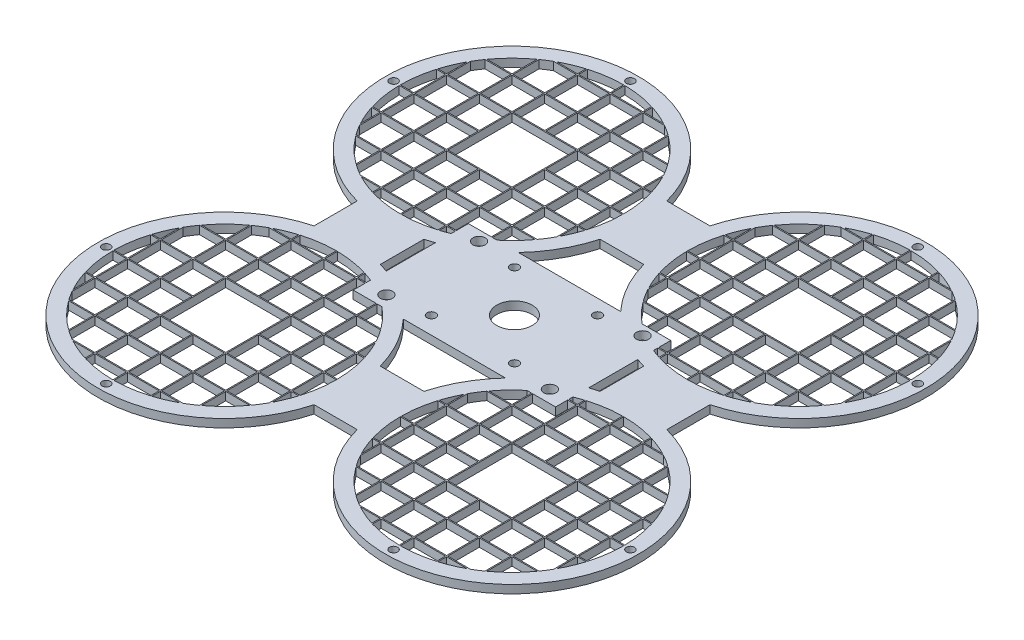
SolidWorks part; units mm, degrees
ref_plane "Front Plane" through (0, 0, 0) normal (0, 0, 1) x (1, 0, 0)
ref_plane "Top Plane" through (0, 0, 0) normal (0, 1, 0) x (1, 0, 0)
ref_plane "Right Plane" through (0, 0, 0) normal (1, 0, 0) x (0, 0, -1)
sketch "Sketch2" plane through (0, 0, 0) normal (0, 1, 0) x (1, 0, 0)
  circle A1 centre (0, 0) radius 41
  circle A2 centre (0, 0) radius 46
  point P208 (0, 0)
extrude "Boss-Extrude2" add sketch "Sketch2" along normal blind 3
sketch "Sketch4" plane through (0, 3, 0) normal (0, 1, 0) x (1, 0, 0)
  line L0 (0, 46) -> (0, 12)
  line L1 (12, 44.4072) -> (12, -44.4072)
  line L2 (24, 39.2428) -> (24, -39.2428)
  line L3 (36, 28.6356) -> (36, -28.6356)
  line L4 (-12, 44.4072) -> (-12, -44.4072)
  line L5 (-24, 39.2428) -> (-24, -32)
  line L6 (-36, 28.6356) -> (-36, -28.6356)
  line L7 (-46, 0) -> (-12, 0)
  line L8 (-44.4072, -12) -> (44.4072, -12)
  line L9 (-39.2428, -24) -> (39.2428, -24)
  line L10 (12, 0) -> (46, 0)
  line L11 (-44.4072, 12) -> (44.4072, 12)
  line L12 (-39.2428, 24) -> (39.2428, 24)
  line L13 (-28.6356, 36) -> (28.6356, 36)
  line L14 (-16, -36) -> (28.6356, -36)
  line L15 (0, -12) -> (0, -46)
  line L50 (-26.0661, -32) -> (-16, -32)
  line L52 (-26.0661, -32) -> (-26.0661, -37.902)
  line L60 (-16, -32) -> (-16, -43.1277)
  line L61 (-28.6356, -36) -> (-26.0661, -36) [skipped]
  circle A1 centre (0, 0) radius 46 construction
  circle A2 centre (0, 0) radius 46
  dimension "D1" = 4
  dimension "D2" = 4
extrude "Extrude-Thin5" add sketch "Sketch4" against normal blind 3 thin thin type one direction wall 0.4
sketch "Sketch5" plane through (0, 0, 0) normal (0, -1, 0) x (1, 0, 0)
  circle A0 centre (0, -43.4524) radius 1.5
  circle A3 centre (43.4524, 0) radius 1.5
  circle A4 centre (0, 43.4524) radius 1.5 [skipped]
  circle A5 centre (-43.4524, 0) radius 1.5 [skipped]
  point P11 (0, 0)
  dimension "D1" = 4
extrude "Cut-Extrude1" cut sketch "Sketch5" against normal blind 3
sketch "Sketch8" plane through (0, 3, 0) normal (0, 1, 0) x (1, 0, 0)
  line L1 (-16, -32) -> (-25.632, -32)
  line L2 (-16, -32) -> (-16, -37.7492)
  line L3 (-16, -37.7492) -> (-25.632, -37.7492)
  line L4 (-25.632, -32) -> (-25.632, -37.7492)
extrude "Boss-Extrude4" add sketch "Sketch8" against normal through all
sketch "Sketch9" plane through (0, 3, 0) normal (0, 1, 0) x (1, 0, 0)
  circle A3 centre (-22.2697, -36.1812) radius 2.25
extrude "Cut-Extrude3" cut sketch "Sketch9" against normal through all
ref_plane "Plane1" through (-52.73, 0, 0) normal (1, 0, 0) x (0, 0, -1)
mirror "Mirror1" about plane through (-52.73, 0, 0) normal (1, 0, 0) of bodies 159
sketch "Sketch10" plane through (0, 3, 0) normal (0, 1, 0) x (1, 0, 0)
  line L0 (-66.2554, 12) -> (-69.06, 12) construction
  line L1 (-63.5152, 12) -> (-41.7915, 12)
  line L2 (-63.5152, 12) -> (-63.5152, -12.4)
  line L3 (-63.5152, -12.4) -> (-41.7915, -12.4)
  line L4 (-41.7915, 12) -> (-41.7915, -12.4)
  line L5 (-66.3801, -12.4) -> (-69.06, -12.4) construction
extrude "Boss-Extrude5" add sketch "Sketch10" against normal up to surface (3 mm away) up to face at (-22.2697, 0, 38.4312)
ref_plane "Plane2" through (0, 0, 52.73) normal (0, 0, 1) x (1, 0, 0)
mirror "Mirror2" about plane through (0, 0, 52.73) normal (0, 0, 1) of bodies 177
sketch "Sketch11" plane through (0, 3, 0) normal (0, 1, 0) x (1, 0, 0)
  line L0 (-93.06, -36.4) -> (-93.06, -39.0799) construction
  line L1 (-117.46, -41.6571) -> (-93.06, -41.6571)
  line L2 (-117.46, -41.6571) -> (-117.46, -63.409)
  line L3 (-117.46, -63.409) -> (-93.06, -63.409)
  line L4 (-93.06, -41.6571) -> (-93.06, -63.409)
  line L5 (-117.46, -36.4) -> (-117.46, -39.2046) construction
extrude "Boss-Extrude6" add sketch "Sketch11" against normal up to surface (3 mm away) up to face at (-52.73, 0, -0.0036)
sketch "Sketch12" plane through (0, 3, 0) normal (0, 1, 0) x (1, 0, 0)
  line L0 (12, -36.4) -> (12, -39.2046) construction
  line L1 (-12.4, -42.0227) -> (12, -42.0227)
  line L2 (-12.4, -42.0227) -> (-12.4, -63.5098)
  line L3 (-12.4, -63.5098) -> (12, -63.5098)
  line L4 (12, -42.0227) -> (12, -63.5098)
  line L5 (-12.4, -36.4) -> (-12.4, -39.0799) construction
extrude "Boss-Extrude7" add sketch "Sketch12" against normal up to surface (3 mm away) up to face at (-62.5401, 0, 52.73)
sketch "Sketch13" plane through (0, 0, 0) normal (0, -1, 0) x (1, 0, 0)
  line L1 (-89.86, 73.86) -> (-15.6, 73.86)
  line L2 (-89.86, 73.86) -> (-89.86, 31.6)
  line L3 (-89.86, 31.6) -> (-15.6, 31.6)
  line L4 (-15.6, 73.86) -> (-15.6, 31.6)
extrude "Boss-Extrude8" add sketch "Sketch13" against normal up to surface (3 mm away) up to face at (-52.73, 3, 52.73)
sketch "Sketch14" plane through (0, 0, 0) normal (0, -1, 0) x (1, 0, 0)
  circle A0 centre (-52.2696, 52.2786) radius 6.495 construction
  circle A1 centre (-52.2696, 52.2786) radius 6.495
extrude "Cut-Extrude4" cut sketch "Sketch14" against normal up to next
sketch "Sketch15" plane through (0, 0, 0) normal (0, -1, 0) x (1, 0, 0)
  circle A0 centre (-37.0195, 37.0287) radius 1.6 construction
  circle A1 centre (-67.5195, 37.0285) radius 1.6 construction
  circle A2 centre (-67.5197, 67.5285) radius 1.6 construction
  circle A3 centre (-37.0197, 67.5287) radius 1.6 construction
  circle A4 centre (-37.0195, 37.0287) radius 1.6
  circle A5 centre (-67.5195, 37.0285) radius 1.6
  circle A6 centre (-67.5197, 67.5285) radius 1.6
  circle A7 centre (-37.0197, 67.5287) radius 1.6
extrude "Cut-Extrude5" cut sketch "Sketch15" against normal up to next
ref_plane "Plane3" through (-32.7695, 23.8804, 37.0287) normal (0, 0, 1) x (1, 0, 0)
ref_plane "Plane4" through (-43.6196, 7.6858, 52.7186) normal (0, 0, 1) x (1, 0, 0)
sketch "Sketch18" plane through (0, 0, 0) normal (0, -1, 0) x (1, 0, 0)
  circle A0 centre (-22.2697, 69.2788) radius 2.25 construction
  circle A1 centre (-22.2695, 35.2788) radius 2.25 construction
  circle A2 centre (-82.2695, 35.2784) radius 2.25 construction
  circle A3 centre (-82.2697, 69.2784) radius 2.25 construction
  circle A4 centre (-22.2697, 69.2788) radius 2.25
  circle A5 centre (-22.2695, 35.2788) radius 2.25
  circle A6 centre (-82.2695, 35.2784) radius 2.25
  circle A7 centre (-82.2697, 69.2784) radius 2.25
extrude "Cut-Extrude6" cut sketch "Sketch18" against normal up to next
